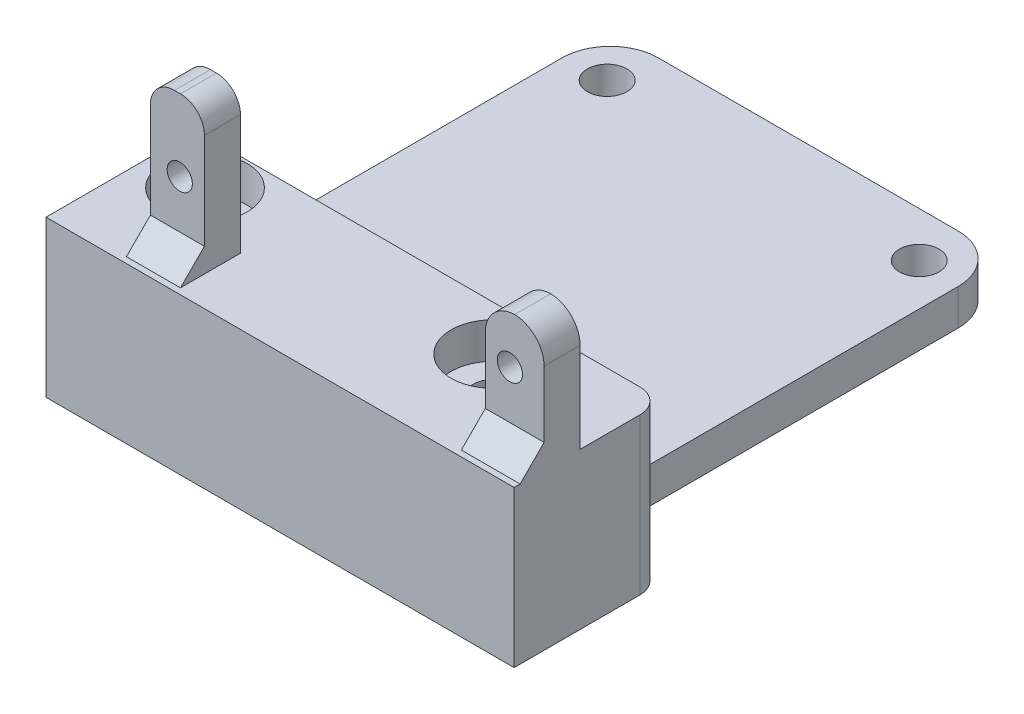
SolidWorks part; units mm, degrees
ref_plane "Front Plane" through (0, 0, 0) normal (0, 0, 1) x (1, 0, 0)
ref_plane "Top Plane" through (0, 0, 0) normal (0, 1, 0) x (1, 0, 0)
ref_plane "Right Plane" through (0, 0, 0) normal (1, 0, 0) x (0, 0, -1)
sketch "Sketch1" plane through (0, 0, 0) normal (0, 1, 0) x (1, 0, 0)
  line L1 (0, 0) -> (33, 0)
  line L2 (0, 0) -> (0, 42)
  line L3 (0, 42) -> (33, 42)
  line L4 (33, 0) -> (33, 42)
  dimension "D1" = 42
  dimension "D2" = 33
extrude "Boss-Extrude1" add sketch "Sketch1" along normal blind 5
ref_plane "Plane1" through (23, 2, -42) normal (1, 0, 0) x (0, 0, -1)
sketch "Sketch4" plane through (0, 5, 0) normal (0, 1, 0) x (1, 0, 0)
  circle A0 centre (4.5, 3.75) radius 1.65 construction
  circle A1 centre (3.5, 38.25) radius 1.65 construction
  circle A2 centre (29.5, 38.25) radius 1.65 construction
  circle A3 centre (28.5, 3.75) radius 1.65 construction
  circle A4 centre (4.5, 3.75) radius 1.65
  circle A5 centre (3.5, 38.25) radius 1.65
  circle A6 centre (29.5, 38.25) radius 1.65
  circle A7 centre (28.5, 3.75) radius 1.65
extrude "Cut-Extrude1" cut sketch "Sketch4" against normal blind 10
sketch "Sketch6" plane through (0, 5, 0) normal (0, 1, 0) x (1, 0, 0)
  line L0 (33, 0) -> (33, 42) construction
  line L1 (33, 0) -> (39, 0)
  line L2 (33, 0) -> (33, 7.4907)
  line L3 (33, 7.4907) -> (39, 7.4907)
  line L4 (39, 0) -> (39, 7.4907)
  line L5 (39, -5) -> (0, -5)
  line L6 (39, -5) -> (39, 0)
  line L7 (39, 0) -> (0, 0)
  line L8 (0, -5) -> (0, 0)
  line M11 (0, 0) -> (33, 0)
  line M12 (33, 0) -> (33, 42)
  dimension "D1" = 5
  dimension "D2" = 6
extrude "Boss-Extrude2" add sketch "Sketch6" against normal blind 5 contours L1 L4 L3 M12 | L8 L5 L6 L1 M11 region at (36, 5, -3.7453) region at (19.5, 5, 2.5)
sketch "Sketch8" plane through (0, 5, 0) normal (0, 1, 0) x (1, 0, 0)
  line L6 (39, 7.4907) -> (33, 7.4907)
  line L7 (33, 7.4907) -> (33, 42)
  line L8 (33, 42) -> (0, 42)
  line L9 (0, 42) -> (0, -5)
  line L10 (0, -5) -> (39, -5)
  line L11 (39, -5) -> (39, 7.4907)
  line L12 (39, 7.4907) -> (33, 7.4907)
  line L13 (33, 7.4907) -> (33, 42)
  line L14 (33, 42) -> (0, 42)
  line L15 (0, 42) -> (0, -5)
  line L16 (0, -5) -> (39, -5)
  line L17 (39, -5) -> (39, 7.4907)
  circle A0 centre (29.5, 38.25) radius 1.65 construction
  circle A1 centre (3.5, 38.25) radius 1.65 construction
  circle A2 centre (4.5, 3.75) radius 1.65 construction
  circle A3 centre (28.5, 3.75) radius 1.65 construction
  circle A4 centre (29.5, 38.25) radius 1.65
  circle A5 centre (3.5, 38.25) radius 1.65
  circle A6 centre (4.5, 3.75) radius 1.65
  circle A7 centre (28.5, 3.75) radius 1.65
  dimension "D1" = 0
extrude "Boss-Extrude4" add sketch "Sketch8" along normal blind 10
sketch "Sketch9" plane through (0, 15, 0) normal (0, 1, 0) x (1, 0, 0)
  line L0 (39, -5) -> (39, 7.4907) construction
  line L1 (39, 0.5) -> (34.1, 0.5)
  line L2 (39, 0.5) -> (39, -2.5)
  line L3 (39, -2.5) -> (34.1, -2.5)
  line L4 (34.1, 0.5) -> (34.1, -2.5)
  line L5 (0, -5) -> (39, -5) construction
  dimension "D1" = 3
  dimension "D2" = 2.5
  dimension "D3" = 4.9
extrude "Boss-Extrude5" add sketch "Sketch9" along normal blind 10
fillet "Fillet2" radius 2.5 2 edges at (34.1, 25, 1) (39, 25, 1)
sketch "Sketch10" plane through (0, 0, -0.5) normal (0, 0, -1) x (-1, 0, 0)
  arc A0 (-37.0682, 20.5) -> (-37.0682, 21.5) centre (-36.1449, 21) ccw construction
  arc A1 (-37.0682, 20.5) -> (-37.0682, 21.5) centre (-36.1449, 21) ccw
  circle A2 centre (-36.1449, 21) radius 1.05
extrude "Cut-Extrude3" cut sketch "Sketch10" against normal blind 10 contours A1 A2 region at (36.1449, 21, -0.5)
sketch "Sketch11" plane through (0, 15, 0) normal (0, 1, 0) x (1, 0, 0)
  line L1 (0, 42) -> (33, 42)
  line L2 (0, 42) -> (0, 7.4907)
  line L3 (0, 7.4907) -> (33, 7.4907)
  line L4 (33, 42) -> (33, 7.4907)
extrude "Cut-Extrude4" cut sketch "Sketch11" against normal blind 10
fillet "Fillet3" radius 4 3 edges at (33, 2.5, -7.4907) (0, 2.5, -42) (33, 2.5, -42)
fillet "Fillet4" radius 2 1 edges at (39, 7.5, -7.4907)
fillet "Fillet5" radius 4 1 edges at (18.5, 5, -7.4907)
sketch "Sketch12" plane through (0, 15, 0) normal (0, 1, 0) x (1, 0, 0)
  circle A0 centre (4.5, 3.75) radius 3.5
  circle A1 centre (28.5, 3.75) radius 3.5
  dimension "D1" = 7
  dimension "D2" = 7
extrude "Cut-Extrude5" cut sketch "Sketch12" against normal blind 3
sketch "Sketch13" plane through (0, 15, 0) normal (0, 1, 0) x (1, 0, 0)
  line L0 (0, 7.4907) -> (0, -5) construction
  line L1 (10.7, 0.5) -> (6.2, 0.5)
  line L2 (10.7, 0.5) -> (10.7, -2.5)
  line L3 (10.7, -2.5) -> (6.2, -2.5)
  line L4 (6.2, 0.5) -> (6.2, -2.5)
  line L5 (6.3699, 0.5) -> (11.1449, 0.5) construction
  dimension "D1" = 4.5
  dimension "D2" = 6.2
  dimension "D3" = 3
  dimension "D4" = 0
extrude "Boss-Extrude6" add sketch "Sketch13" along normal up to surface (12 mm away)
fillet "Fillet6" radius 2 2 edges at (6.2, 27, 1) (10.7, 27, 1)
sketch "Sketch14" plane through (0, 0, -0.5) normal (0, 0, -1) x (-1, 0, 0)
  arc A0 (-7.7216, 21.5) -> (-7.7216, 20.5) centre (-8.6449, 21) ccw construction
  arc A1 (-7.7216, 21.5) -> (-7.7216, 20.5) centre (-8.6449, 21) ccw
  circle A2 centre (-8.6449, 21) radius 1.05
extrude "Cut-Extrude6" cut sketch "Sketch14" against normal blind 7 contours A1 A2 region at (8.6449, 21, -0.5)
chamfer "Chamfer1" distance 2 angle 45 2 edges at (36.55, 15, 2.5) (8.45, 15, 2.5)
sketch "Sketch15" plane through (0, 0, 0) normal (0, -1, 0) x (1, 0, 0)
  line L5 (39, -5.4907) -> (39, 5)
  line L6 (39, 5) -> (0, 5)
  line L7 (0, 5) -> (0, -38)
  line L8 (4, -42) -> (29, -42)
  line L9 (33, -38) -> (33, -11.4907)
  line L10 (39, -5.4907) -> (39, 5)
  line L11 (39, 5) -> (0, 5)
  line L12 (0, 5) -> (0, -38)
  line L13 (4, -42) -> (29, -42)
  line L14 (33, -38) -> (33, -11.4907)
  arc A4 (37, -7.4907) -> (33, -11.4907) centre (37, -11.4907) ccw
  arc A5 (37, -7.4907) -> (39, -5.4907) centre (37, -5.4907) ccw
  arc A6 (0, -38) -> (4, -42) centre (4, -38) ccw
  arc A7 (29, -42) -> (33, -38) centre (29, -38) ccw
  arc A8 (37, -7.4907) -> (33, -11.4907) centre (37, -11.4907) ccw
  arc A9 (37, -7.4907) -> (39, -5.4907) centre (37, -5.4907) ccw
  arc A10 (0, -38) -> (4, -42) centre (4, -38) ccw
  arc A11 (29, -42) -> (33, -38) centre (29, -38) ccw
  dimension "D1" = 0
extrude "Cut-Extrude7" cut sketch "Sketch15" against normal blind 2
